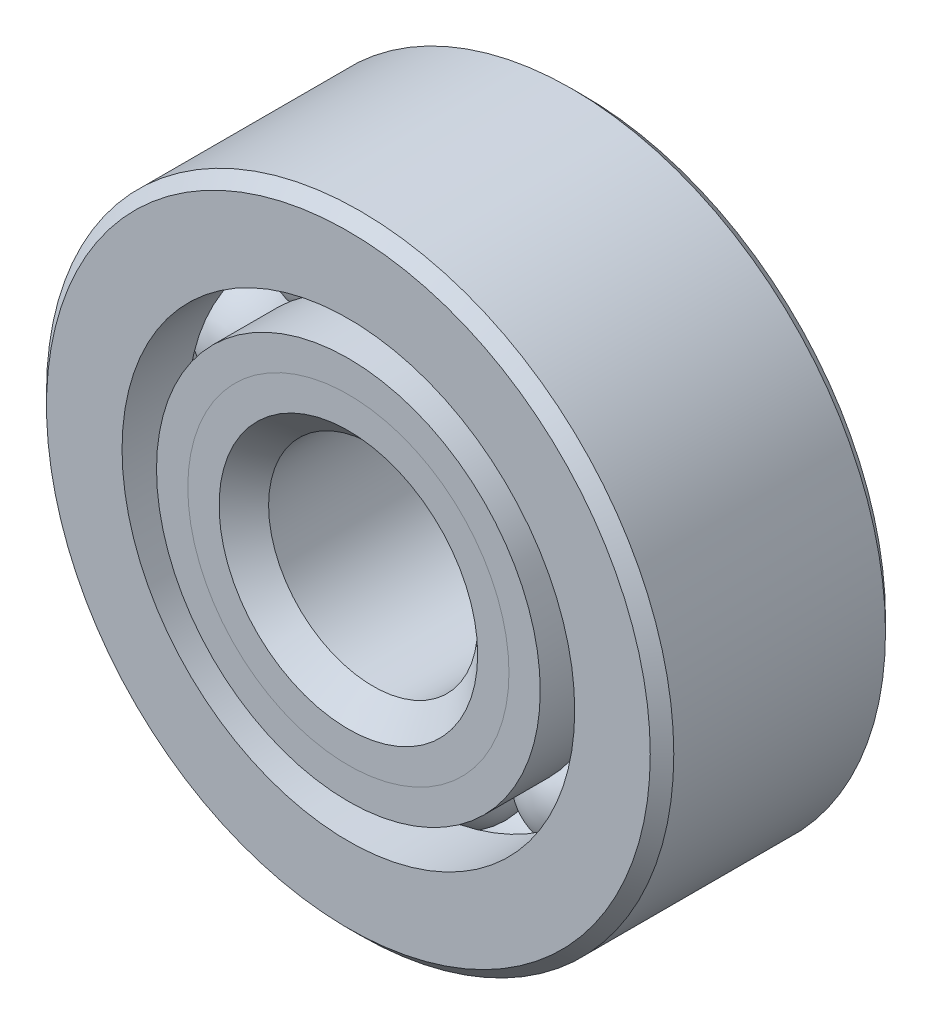
SolidWorks part; units mm, degrees
ref_plane "Front Plane" through (0, 0, 0) normal (0, 0, 1) x (1, 0, 0)
ref_plane "Top Plane" through (0, 0, 0) normal (0, 1, 0) x (1, 0, 0)
ref_plane "Right Plane" through (0, 0, 0) normal (1, 0, 0) x (0, 0, -1)
sketch "Sketch1" plane through (0, 0, 0) normal (1, 0, 0) x (0, 0, -1)
  line L0 (-3.5719, 0) -> (3.5719, 0) construction
  line L1 (0, 9.525) -> (0, -9.525) construction
  line L2 (3.2147, 9.525) -> (-3.2147, 9.525)
  line L3 (-3.2147, 9.525) -> (-3.5719, 9.1678)
  line L4 (-3.5719, 9.1678) -> (-3.5719, 6.8734)
  line L5 (-3.5719, 6.8734) -> (-1.5875, 6.8734)
  line L6 (3.5719, 6.8734) -> (1.5875, 6.8734)
  line L7 (3.5719, 9.1678) -> (3.5719, 6.8734)
  line L8 (3.2147, 9.525) -> (3.5719, 9.1678)
  line L9 (0, 9.525) -> (0, 6.35) construction
  line L10 (0, 6.35) -> (0, 3.175) construction
  arc A0 (-1.5875, 6.8734) -> (1.5875, 6.8734) centre (0, 6.35) cw
  point P14 (0, 3.175)
  dimension "Width" = 7.1437
  dimension "OD" = 19.05
  dimension "D1" = 45
  dimension "D2" = 0.3572
  dimension "D3" = 3.175
  dimension "D4" = 0.5234
revolve "Revolve1" add sketch "Sketch1" angle 360 about L0
sketch "Sketch2" plane through (0, 0, 0) normal (1, 0, 0) x (0, 0, -1)
  line L0 (-3.5719, 5.8266) -> (-1.5875, 5.8266)
  line L1 (-3.5719, 9.1678) -> (-3.5719, -9.1678) construction
  line L2 (-3.5719, 5.8266) -> (-3.5719, 4.8767)
  line L3 (-3.5719, 4.8767) -> (-2.6219, 3.9267)
  line L4 (-2.6219, 3.9267) -> (0, 3.9267)
  line L5 (0, 9.525) -> (0, -9.525) construction
  line L6 (0, 3.9267) -> (0, 4.6785)
  line L7 (0, 4.6785) -> (0, 3.175) construction
  line L8 (-3.5719, 5.8266) -> (-3.5719, 3.9267) construction
  line L9 (-3.5719, 3.9267) -> (-2.6219, 3.9267) construction
  arc A0 (-1.5875, 5.8266) -> (0, 4.6785) centre (0, 6.35) ccw
  arc A1 (1.5875, 6.8734) -> (-1.5875, 6.8734) centre (0, 6.35) ccw construction
  circle A2 centre (0, 6.35) radius 1.6715 construction
  dimension "D1" = 45
revolve "Revolve2" add sketch "Sketch2" angle 360 about L0
sketch "Sketch3" plane through (0, 0, 0) normal (1, 0, 0) x (0, 0, -1)
  line L0 (-3.5719, 4.8767) -> (-2.6219, 3.9267)
  line L1 (-2.6219, 3.9267) -> (0, 3.9267)
  line L2 (0, 3.9267) -> (0, 4.6785)
  line L3 (-3.5719, 4.8767) -> (-3.5719, 3.9267)
  line L4 (-3.5719, 5.8266) -> (-3.5719, 3.9267) construction
  line L5 (-3.5719, 3.9267) -> (-2.8201, 3.175)
  line L6 (-2.8201, 3.175) -> (3.2147, 3.175)
  line L7 (3.2147, 9.525) -> (3.2147, -9.525) construction
  line L8 (3.2147, 3.175) -> (3.5719, 3.5322)
  line L9 (3.5719, -9.1678) -> (3.5719, 9.1678) construction
  line L10 (3.5719, 3.5322) -> (3.5719, 5.8266)
  line L11 (3.5719, 5.8266) -> (1.5875, 5.8266)
  line L13 (3.2147, 9.525) -> (3.5719, 9.1678) construction
  circle A0 centre (0, 6.35) radius 1.6715 construction
  arc A1 (1.5875, 5.8266) -> (0, 4.6785) centre (0, 6.35) cw
revolve "Revolve3" add sketch "Sketch3" angle 360 about L0
sketch "Sketch4" plane through (0, 0, 0) normal (1, 0, 0) x (0, 0, -1)
  line L0 (-1.6715, 6.35) -> (1.6715, 6.35)
  circle A1 centre (0, 6.35) radius 1.6715 construction
  arc A2 (-1.6715, 6.35) -> (1.6715, 6.35) centre (0, 6.35) cw
  arc A3 (1.5875, 6.8734) -> (-1.5875, 6.8734) centre (0, 6.35) ccw construction
revolve "Revolve4" add sketch "Sketch4" angle 360 about L0
ref_axis "Axis1" through (0, 0, -3.5719) along (0, 0, 1)
pattern_circular "CirPattern1" count 10 every 36 about axis through (0, 0, -3.5719) along (0, 0, 1) of bodies 104
equation "\"D2@Sketch1\" = \"Width@Sketch1\"*.05"
equation "\"D3@Sketch1\" = \"Width@Sketch1\"/2.25"
equation "\"D4@Sketch1\" = (((\"OD@Sketch1\"-\"Width@Sketch1\")/2)/3.25)/3.5"
equation "\"D2@CirPattern1\" = 360/\"Balls@CirPattern1\""
